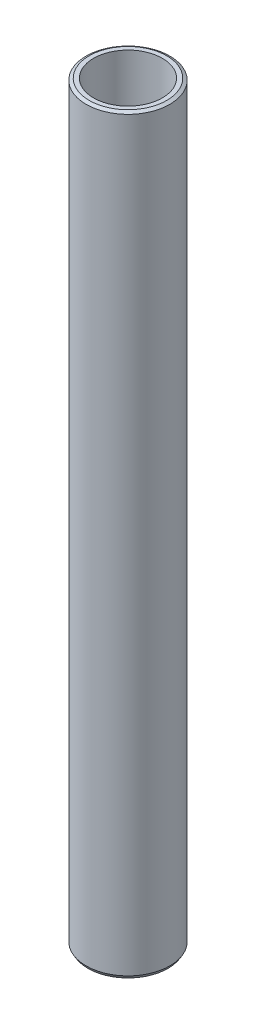
SolidWorks part; units mm, degrees
ref_plane "Front Plane" through (0, 0, 0) normal (0, 0, 1) x (1, 0, 0)
ref_plane "Top Plane" through (0, 0, 0) normal (0, 1, 0) x (1, 0, 0)
ref_plane "Right Plane" through (0, 0, 0) normal (1, 0, 0) x (0, 0, -1)
sketch "Sketch1" plane through (0, 0, 0) normal (0, 1, 0) x (1, 0, 0)
  circle A0 centre (0, 0) radius 30
  dimension "SHAFT_OD" = 60
extrude "Boss-Extrude1" add sketch "Sketch1" along normal blind 538.2455
sketch "Sketch2" plane through (0, 0, 0) normal (0, 1, 0) x (1, 0, 0)
  circle A0 centre (0, 0) radius 24.6409
  dimension "BORE_D" = 49.2818
extrude "Cut-Extrude1" cut sketch "Sketch2" along normal through all
chamfer "Chamfer1" distance 1.2857 angle 60 2 edges at (0, 538.2455, 30) (0, 0, 30) first distance on face at (0, 538.2455, 30) first distance on face at (0, 0, 24.6409)
